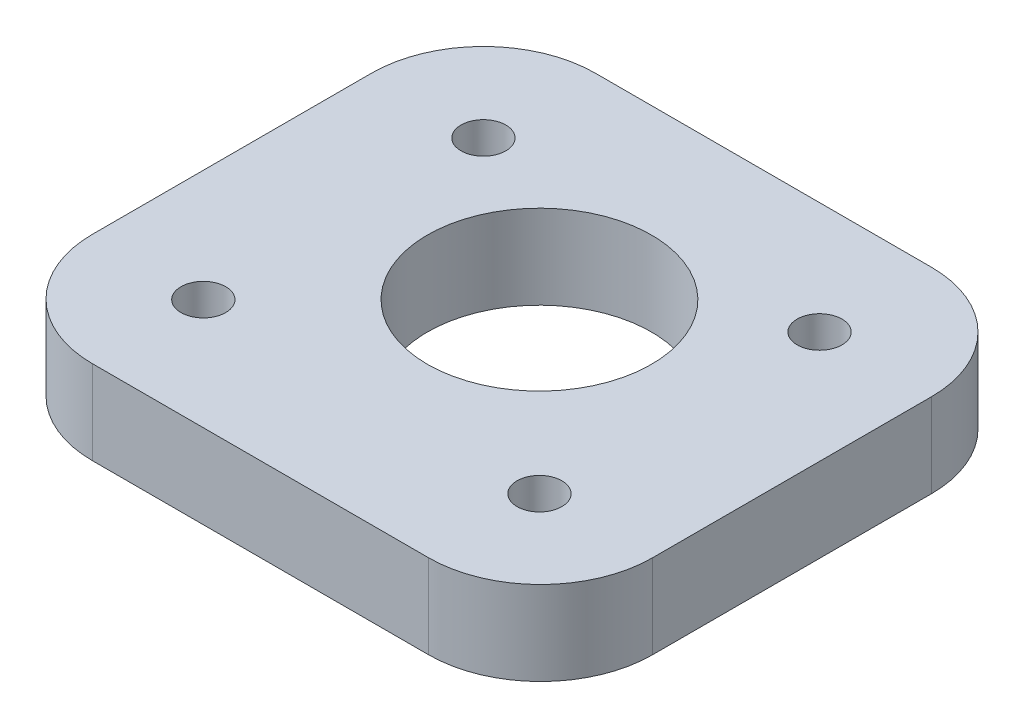
SolidWorks part; units mm, degrees
ref_plane "Front Plane" through (0, 0, 0) normal (0, 0, 1) x (1, 0, 0)
ref_plane "Top Plane" through (0, 0, 0) normal (0, 1, 0) x (1, 0, 0)
ref_plane "Right Plane" through (0, 0, 0) normal (1, 0, 0) x (0, 0, -1)
sketch "Sketch1" plane through (0, 0, 0) normal (0, 1, 0) x (1, 0, 0)
  line L0 (0, -111.3091) -> (63.5, -111.3091)
  line L1 (0, 2.9909) -> (63.5, 2.9909)
  line L2 (0, 2.9909) -> (0, -124.0091)
  line L3 (0, -124.0091) -> (63.5, -124.0091)
  line L4 (63.5, 2.9909) -> (63.5, -124.0091)
  line L7 (0, -60.3821) -> (63.5, -60.3821)
  circle A0 centre (31.75, -22.4091) radius 15.875
  circle A1 centre (12.7, -86.1631) radius 2.4892
  circle A2 centre (25.4, -86.1631) radius 2.4892
  circle A3 centre (38.1, -86.1631) radius 2.4892
  circle A4 centre (50.8, -86.1631) radius 2.4892
  dimension "D3" = 31.75
  dimension "D4" = 25.4
  dimension "D5" = 31.75
  dimension "D6" = 4.9784
  dimension "D7" = 12.7
  dimension "D8" = 37.846
  dimension "D1" = 63.5
  dimension "D2" = 127
  dimension "D10" = 12.7
  dimension "D12" = 63.627
  dimension "D9" = 4
extrude "Boss-Extrude2" add sketch "Sketch1" along normal blind 9.525 contours L4 L0 L2 L3 | L2 L7 L4 L1 A0 region at (31.75, 0, 117.6591) region at (0.8971, 0, 28.6956)
extrude "Boss-Extrude3" add sketch "Sketch1<3>" along normal blind 3.175 contours L7 L2 L0 L4 A4 A3 A2 A1 region at (31.75, 0, 85.8377)
sketch "Sketch1<3>" plane through (0, 0, 0) normal (0, 1, 0) x (1, 0, 0) same geometry as "Sketch1"
fillet "Fillet2" radius 12.7 4 edges at (0, 4.7625, 124.0091) (63.5, 4.7625, 124.0091) (0, 4.7625, -2.9909) (63.5, 4.7625, -2.9909)
sketch "Sketch2" plane through (0, 0, 0) normal (0, -1, 0) x (1, 0, 0)
  circle A0 centre (12.7, 41.4591) radius 2.54
  circle A1 centre (50.8, 41.4591) radius 2.54
  circle A2 centre (50.8, 9.7091) radius 2.54
  circle A3 centre (12.7, 9.7091) radius 2.54
  arc A8 (0, 9.7091) -> (12.7, -2.9909) centre (12.7, 9.7091) ccw construction
  arc A9 (50.8, -2.9909) -> (63.5, 9.7091) centre (50.8, 9.7091) ccw construction
  dimension "D1" = 5.08
  dimension "D2" = 31.75
extrude "Cut-Extrude1" cut sketch "Sketch2" against normal through all
sketch "Sketch3" plane through (0, 9.525, 0) normal (0, 1, 0) x (1, 0, 0)
  line L1 (0, -60.3821) -> (69.3277, -60.3821)
  line L2 (0, -60.3821) -> (0, -128.0915)
  line L3 (0, -128.0915) -> (69.3277, -128.0915)
  line L4 (69.3277, -60.3821) -> (69.3277, -128.0915)
  line L5 (0, -60.3821) -> (84.7064, -60.3821)
  line L6 (0, -60.3821) -> (0, -54.0321)
  line L7 (0, -54.0321) -> (84.7064, -54.0321)
  line L8 (84.7064, -60.3821) -> (84.7064, -54.0321)
  line M5 (63.5, -111.3091) -> (0, -111.3091)
  arc M6 (0, -111.3091) -> (12.7, -124.0091) centre (12.7, -111.3091) ccw
  line M7 (12.7, -124.0091) -> (50.8, -124.0091)
  arc M8 (50.8, -124.0091) -> (63.5, -111.3091) centre (50.8, -111.3091) ccw
  dimension "D1" = 6.35
extrude "Cut-Extrude2" cut sketch "Sketch3" against normal through all contours L5 L8 L7 L6 L1 | M8 M5 M6 M7 | L4 L1 L2 L3 M5 M8 M7 M6 region at (42.3532, 9.525, 57.2071) region at (31.75, 9.525, 117.3292) region at (35.2067, 9.525, 89.9344)
fillet "Fillet3" radius 12.7 2 edges at (63.5, 4.7625, 54.0321) (0, 4.7625, 54.0321)
sketch "Sketch4" plane through (0, 9.525, 0) normal (0, 1, 0) x (1, 0, 0)
  circle A0 centre (31.75, -22.4091) radius 12.7
  circle A1 centre (31.75, -22.4091) radius 15.875 construction
  circle A2 centre (31.75, -22.4091) radius 15.875
  circle M5 centre (31.75, -22.4091) radius 15.875
  dimension "D1" = 25.4
extrude "Boss-Extrude4" add sketch "Sketch4" against normal up to surface (9.525 mm away) contours A0 M5 region at (16.324, 9.525, 22.4091) up to face at (31.75, 0, 38.2841)
